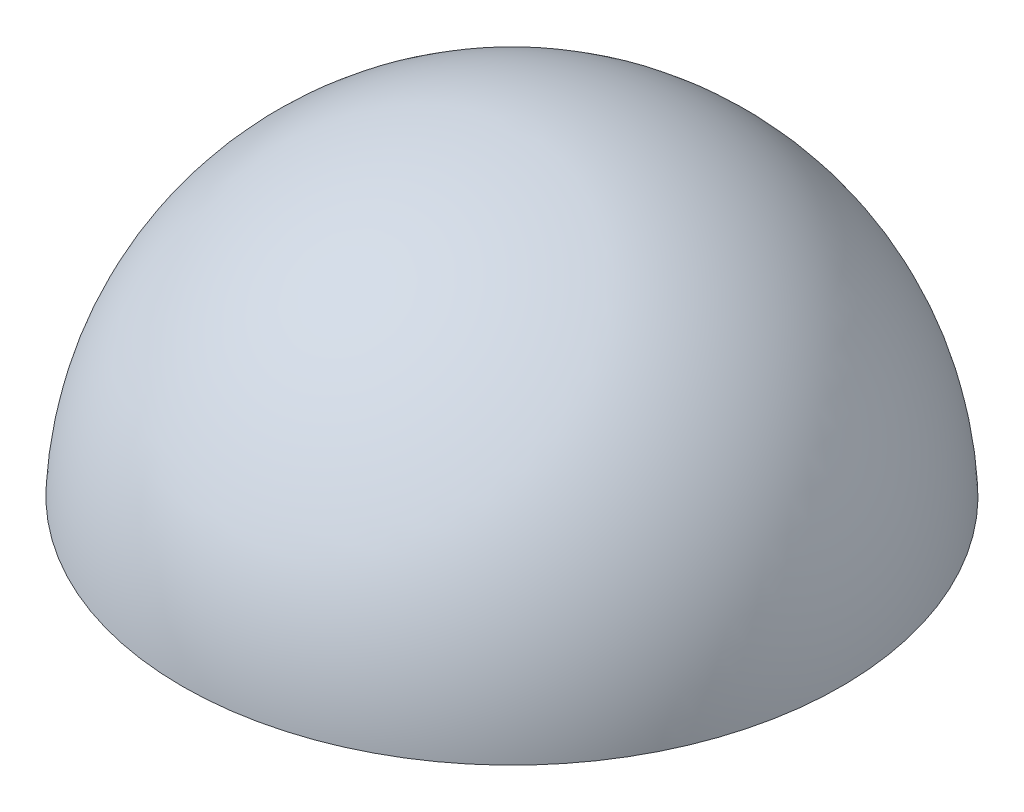
SolidWorks part; units mm, degrees
ref_plane "Front Plane" through (0, 0, 0) normal (0, 0, 1) x (1, 0, 0)
ref_plane "Top Plane" through (0, 0, 0) normal (0, 1, 0) x (1, 0, 0)
ref_plane "Right Plane" through (0, 0, 0) normal (1, 0, 0) x (0, 0, -1)
sketch "Sketch1" plane through (0, 0, 0) normal (0, 1, 0) x (1, 0, 0)
  line L0 (0, -44.45) -> (0, 44.45)
  arc A0 (0, 44.45) -> (0, -44.45) centre (0, 0) ccw
  arc A1 (0, 42.45) -> (0, -42.45) centre (0, 0) ccw
  circle A3 centre (0, 0) radius 44.45 construction
  circle A4 centre (0, 0) radius 42.45 construction
  point P1 (42.45, 0)
  point P6 (42.5077, 12.9959)
  dimension "D1" = 88.9
  dimension "D2" = 2
revolve "Revolve1" add sketch "Sketch1" angle 180 about L0 region at (-43.4561, 0, 0)
sketch "Sketch2" plane through (0, 0, 0) normal (0, 1, 0) x (1, 0, 0)
  circle A0 centre (0, 0) radius 44.45
extrude "Cut-Extrude1" cut sketch "Sketch2" along normal blind 2
